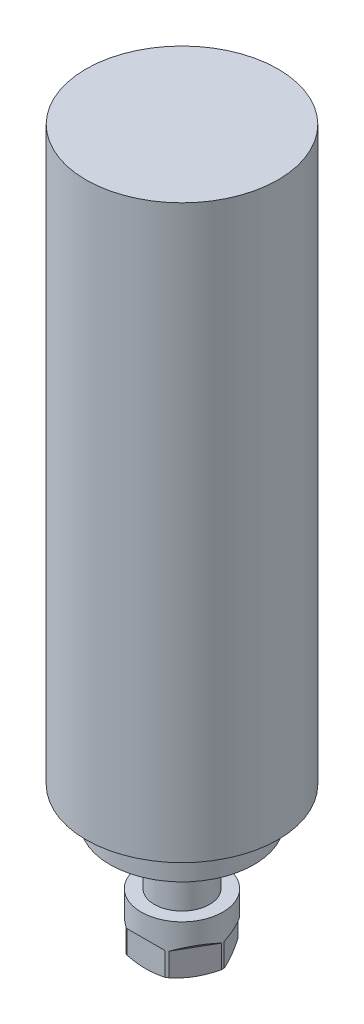
SolidWorks part; units mm, degrees
material "Plain Carbon Steel"
ref_plane "Front Plane" through (0, 0, 0) normal (0, 0, 1) x (1, 0, 0)
ref_plane "Top Plane" through (0, 0, 0) normal (0, 1, 0) x (1, 0, 0)
ref_plane "Right Plane" through (0, 0, 0) normal (1, 0, 0) x (0, 0, -1)
ref_axis "Axis1" through (0, 160.005, 0) along (0, -1, 0)
sketch "Sketch1" plane through (0, 0, 0) normal (1, 0, 0) x (0, 0, -1)
  line L0 (0, 128.3) -> (0, -128.3)
  line L1 (0, 128.3) -> (-39.9, 128.3)
  line L2 (-39.9, 128.3) -> (-39.9, 100.3)
  line L3 (-39.9, 100.3) -> (-40, 100.3)
  line L4 (-40, 100.3) -> (-40, -99.7)
  line L5 (-40, -99.7) -> (-39.9, -99.7)
  line L6 (-39.9, -99.7) -> (-39.9, -109.7)
  line L7 (-39.9, -109.7) -> (-30, -109.7)
  line L8 (-30, -109.7) -> (-30, -123.7)
  line L9 (-30, -123.7) -> (-24.1, -123.7)
  line L10 (-24.1, -123.7) -> (-24.1, -128.3)
  line L11 (-24.1, -128.3) -> (0, -128.3)
  dimension "D1" = 40
  dimension "D2" = 39.9
  dimension "D3" = 39.9
  dimension "D4" = 28
  dimension "D5" = 200
  dimension "D6" = 10
  dimension "D7" = 14
  dimension "D8" = 30
  dimension "D9" = 4.6
  dimension "D10" = 24.1
revolve "Revolve1" add sketch "Sketch1" angle 360 about L0
chamfer "Chamfer2" distance 7 distance2 1.5 1 edges at (0, -128.3, 24.1) first distance on face at (0, -128.3, 24.1)
sketch "Sketch2" plane through (0, -128.3, 0) normal (0, -1, 0) x (1, 0, 0)
  circle A0 centre (0, 0) radius 11.5
  dimension "D1" = 23
extrude "Boss-Extrude1" add sketch "Sketch2" along normal blind 19
chamfer "Chamfer1" [suppressed] distance 1 angle 45
sketch "Sketch3" plane through (0, -147.3, 0) normal (0, -1, 0) x (1, 0, 0)
  circle A0 centre (0, 0) radius 17
  dimension "D1" = 34
extrude "Boss-Extrude2" add sketch "Sketch3" along normal blind 22.5
ref_plane "Plane1" through (21.67, 0, 0) normal (1, 0, 0) x (0, 0, -1)
chamfer "Chamfer3" distance 2 distance2 4 1 edges at (0, -169.8, -17) first distance on face at (0, -169.8, -17)
sketch "Sketch7" plane through (0, 0, 0) normal (1, 0, 0) x (0, 0, -1)
  line L0 (0, -169.8) -> (0, -147.3) construction
  line L1 (-29.8933, -143.3067) -> (-15, -158.2)
  line L2 (-29.8933, -143.3067) -> (-29.8933, -177.0813)
  line L3 (-29.8933, -177.0813) -> (-15, -177.0813)
  line L4 (-15, -158.2) -> (-15, -177.0813)
  line L5 (-17, -169.8) -> (17, -169.8) construction
  line L6 (17, -147.3) -> (-17, -147.3) construction
  dimension "D1" = 45
  dimension "D2" = 15
  dimension "D3" = 11.6
extrude "Cut-Extrude1" cut sketch "Sketch7" against normal through all both and the other way through all
pattern_circular "CirPattern1" count 6 over 360 about axis through (0, 160.005, 0) along (0, -1, 0) of "Cut-Extrude1"
sketch "Sketch9" plane through (0, -169.8, 0) normal (0, -1, 0) x (1, 0, 0)
  circle A0 centre (0, 0) radius 7.7
  dimension "D1" = 15.4
extrude "Cut-Extrude2" [suppressed] cut sketch "Sketch9" against normal blind 10
sketch "Sketch10" plane through (0, 128.3, 0) normal (0, 1, 0) x (1, 0, 0)
  circle A0 centre (0, 0) radius 22
  dimension "D1" = 44
extrude "Boss-Extrude3" [suppressed] add sketch "Sketch10" along normal blind 4.4 draft 22
sketch "Sketch11" plane through (0, 128.3, 0) normal (0, 1, 0) x (1, 0, 0)
  line L0 (-23.6881, 23.6881) -> (-26.5872, 26.5872) construction
  line L1 (23.6881, -23.6881) -> (-23.6881, -23.6881) construction
  line L2 (23.6881, -23.6881) -> (23.6881, 23.6881) construction
  line L3 (23.6881, 23.6881) -> (-23.6881, 23.6881) construction
  line L4 (-23.6881, -23.6881) -> (-23.6881, 23.6881) construction
  line L5 (23.6881, -23.6881) -> (-23.6881, 23.6881) construction
  line L6 (23.6881, 23.6881) -> (-23.6881, -23.6881) construction
  line L7 (-26.5872, 26.5872) -> (-28.2843, 28.2843) construction
  circle A0 centre (-23.6881, 23.6881) radius 4.1
  circle A1 centre (23.6881, 23.6881) radius 4.1
  circle A2 centre (23.6881, -23.6881) radius 4.1
  circle A3 centre (-23.6881, -23.6881) radius 4.1
  circle A4 centre (0, 0) radius 40 construction
  point P0 (0, 0)
  dimension "D1" = 8.2
  dimension "D2" = 2.4
extrude "Cut-Extrude3" [suppressed] cut sketch "Sketch11" against normal blind 10
sketch "Sketch12" plane through (0, 128.3, 0) normal (0, 1, 0) x (1, 0, 0)
  line L0 (0, 0) -> (0, 30.7) construction
  line L1 (0, 30.7) -> (-12.75, 30.7) construction
  line L2 (-12.75, 30.7) -> (-17.75, 30.7) construction
  circle A0 centre (-12.75, 30.7) radius 5
  dimension "D1" = 10
  dimension "D2" = 17.75
  dimension "D3" = 30.7
extrude "Boss-Extrude4" [suppressed] add sketch "Sketch12" along normal blind 5.8
sketch "Sketch13" [suppressed] plane through (0, 134.1, 0) normal (0, 1, 0) x (1, 0, 0)
  line L1 (-19.6782, 30.7) -> (-16.2141, 24.7)
  line L2 (-16.2141, 24.7) -> (-9.2859, 24.7)
  line L3 (-9.2859, 24.7) -> (-5.8218, 30.7)
  line L4 (-5.8218, 30.7) -> (-9.2859, 36.7)
  line L5 (-9.2859, 36.7) -> (-16.2141, 36.7)
  line L6 (-16.2141, 36.7) -> (-19.6782, 30.7)
  circle A0 centre (-12.75, 30.7) radius 6 construction
  dimension "D1" = 12
extrude "Boss-Extrude5" [suppressed] add sketch "Sketch13" along normal blind 4.5
sketch "Sketch14" [suppressed] plane through (0, 138.6, 0) normal (0, 1, 0) x (1, 0, 0)
  circle A0 centre (-12.75, 30.7) radius 5.5
  dimension "D1" = 11
extrude "Boss-Extrude6" [suppressed] add sketch "Sketch14" along normal blind 4
sketch "Sketch15" [suppressed] plane through (0, 142.6, 0) normal (0, 1, 0) x (1, 0, 0)
  line L1 (-20.8329, 30.7) -> (-16.7915, 23.7)
  line L2 (-16.7915, 23.7) -> (-8.7085, 23.7)
  line L3 (-8.7085, 23.7) -> (-4.6671, 30.7)
  line L4 (-4.6671, 30.7) -> (-8.7085, 37.7)
  line L5 (-8.7085, 37.7) -> (-16.7915, 37.7)
  line L6 (-16.7915, 37.7) -> (-20.8329, 30.7)
  circle A0 centre (-12.75, 30.7) radius 7 construction
  dimension "D1" = 14
extrude "Boss-Extrude7" [suppressed] add sketch "Sketch15" along normal blind 12
ref_axis "Axis2" [suppressed] through (-12.75, 167.8718, -30.7) along (0, -1, 0)
ref_plane "Plane2" [suppressed] through (0, 0, -30.7) normal (0, 0, 1) x (0, -1, 0)
sketch "Sketch16" [suppressed] plane through (0, 0, -30.7) normal (0, 0, 1) x (0, -1, 0)
  line L0 (-154.6, -18.75) -> (-150.2, -19.6777)
  line L1 (-150.2, -19.6777) -> (-142.6099, -27.2678)
  line L2 (-142.6099, -27.2678) -> (-154.6, -27.2678)
  line L3 (-154.6, -27.2678) -> (-154.6, -18.75)
  line L4 (-154.6, -12.75) -> (-154.6, -18.75) construction
  line L5 (-154.6, -16.7915) -> (-154.6, -8.7085) construction
  line L6 (-154.6, -20.8329) -> (-154.6, -16.7915) construction
  dimension "D1" = 6
  dimension "D2" = 4.4
  dimension "D3" = 45
revolve "Cut-Revolve1" [suppressed] cut sketch "Sketch16" angle 360 about axis through (-12.75, 167.8718, -30.7) along (0, -1, 0)
sketch "Sketch17" [suppressed] plane through (0, 154.6, 0) normal (0, 1, 0) x (1, 0, 0)
  circle A0 centre (-12.75, 30.7) radius 3.95
  dimension "D1" = 7.9
extrude "Cut-Extrude4" [suppressed] cut sketch "Sketch17" against normal blind 12
mirror "Mirror1" [suppressed] about plane through (0, 0, 0) normal (1, 0, 0)
sketch "Sketch18" [suppressed] plane through (0, 132.7, 0) normal (0, 1, 0) x (1, 0, 0)
  line L1 (14.4, 14.4) -> (-14.4, 14.4)
  line L2 (14.4, 14.4) -> (14.4, -14.4)
  line L3 (14.4, -14.4) -> (-14.4, -14.4)
  line L4 (-14.4, 14.4) -> (-14.4, -14.4)
  line L5 (14.4, 14.4) -> (-14.4, -14.4) construction
  line L6 (14.4, -14.4) -> (-14.4, 14.4) construction
  point P0 (0, 0)
  dimension "D1" = 28.8
extrude "Boss-Extrude8" [suppressed] add sketch "Sketch18" along normal blind 2
fillet "Fillet1" [suppressed] radius 2
sketch "Sketch19" [suppressed] plane through (0, 0, 0) normal (0, 0, 1) x (1, 0, 0)
  line L0 (0, 0) -> (0, 195.8759) construction
  line L1 (0, 134.7) -> (-10.9, 134.7)
  line L2 (-10.9, 134.7) -> (-10.9, 141.3)
  line L3 (-10.9, 141.3) -> (-12.9, 141.3)
  line L4 (-12.9, 141.3) -> (-12.9, 154.1)
  line L5 (-12.9, 154.1) -> (-11.2, 154.1)
  line L6 (-11.2, 154.1) -> (-11.2, 163.4)
  line L7 (-11.2, 163.4) -> (-8.2, 178.4)
  line L8 (-8.2, 178.4) -> (-11, 178.4)
  line L9 (-11, 178.4) -> (-11, 185.5)
  line L10 (-11, 185.5) -> (-6, 185.5)
  line L11 (0, 185.5) -> (0, 134.7)
  line L12 (-14.4, 134.7) -> (14.4, 134.7) construction
  line L13 (-3.8369, 204.5) -> (-3.8369, 195.8759)
  line L14 (-3.8369, 195.8759) -> (0, 195.8759)
  line L15 (0, 185.5) -> (0, 195.8759)
  line L16 (-3.8369, 204.5) -> (-6, 204.5)
  line L17 (-6, 185.5) -> (-6, 204.5)
  line L18 (0, 204.5) -> (0, 319.5248) construction
  line L19 (0, 204.5) -> (0, 195.8759) construction
  dimension "D1" = 10.9
  dimension "D2" = 6.6
  dimension "D3" = 12.9
  dimension "D4" = 12.8
  dimension "D5" = 11.2
  dimension "D6" = 9.3
  dimension "D7" = 15
  dimension "D8" = 7.1
  dimension "D9" = 11
  dimension "D10" = 8.2
  dimension "D11" = 6
  dimension "D12" = 19
revolve "Revolve2" [suppressed] add sketch "Sketch19" angle 360 about L0
sketch "Sketch20" plane through (0, 0, 0) normal (0, 0, 1) x (1, 0, 0)
  line L0 (0, -128.3) -> (0, -147.3) construction
  line L1 (-11.5, -128.3) -> (11.5, -128.3) construction
  line L2 (17, -147.3) -> (-17, -147.3) construction
  line L3 (10.5, -129.3659) -> (10.5, -139.6659)
  line L4 (-21.6678, -129.3659) -> (-10.5, -129.3659)
  line L5 (-21.6678, -129.3659) -> (-21.6678, -139.6659)
  line L6 (-21.6678, -139.6659) -> (-10.5, -139.6659)
  line L7 (-10.5, -129.3659) -> (-10.5, -139.6659)
  line L8 (21.6678, -139.6659) -> (10.5, -139.6659)
  line L9 (21.6678, -129.3659) -> (21.6678, -139.6659)
  line L10 (21.6678, -129.3659) -> (10.5, -129.3659)
  dimension "D1" = 10.5
  dimension "D2" = 10.3
extrude "Cut-Extrude5" [suppressed] cut sketch "Sketch20" against normal through all both and the other way through all
sketch "Sketch21" plane through (0, 128.3, 0) normal (0, 1, 0) x (1, 0, 0)
  circle A0 centre (0, 0) radius 40 construction
  circle A1 centre (0, 0) radius 40
extrude "Boss-Extrude9" add sketch "Sketch21" against normal up to surface (238 mm away) up to face at (0, -109.7, 30)
